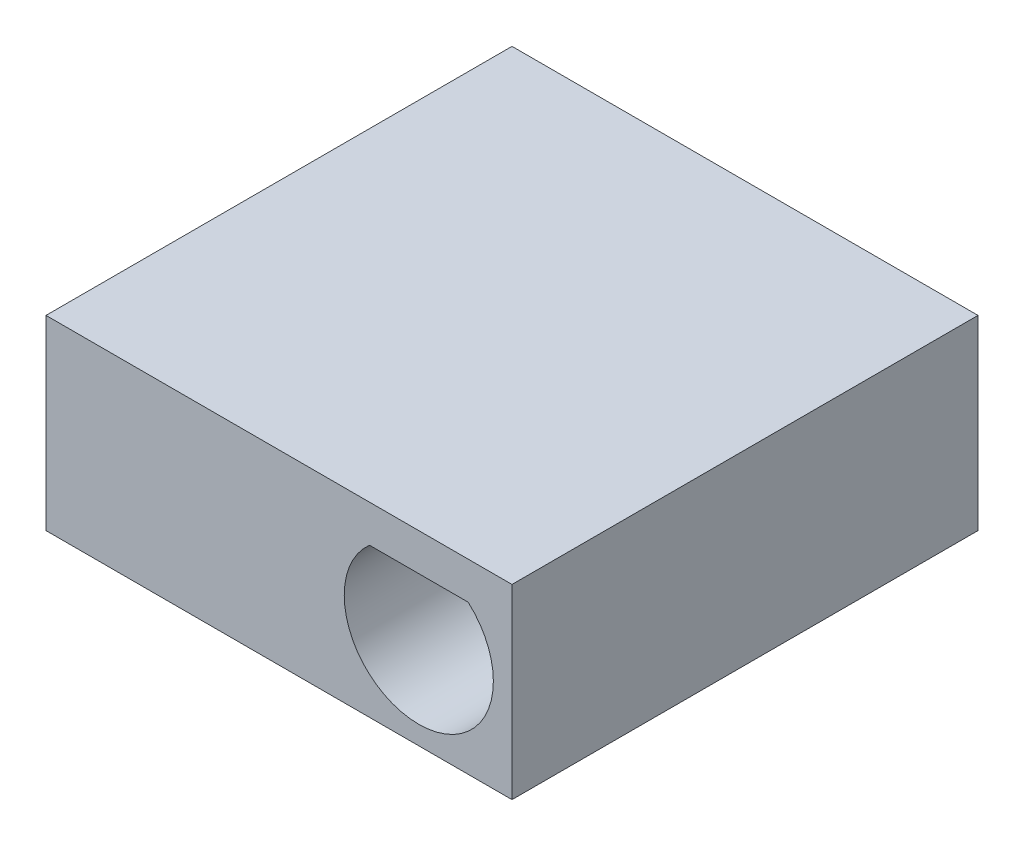
SolidWorks part; units mm, degrees
ref_plane "Front Plane" through (0, 0, 0) normal (0, 0, 1) x (1, 0, 0)
ref_plane "Top Plane" through (0, 0, 0) normal (0, 1, 0) x (1, 0, 0)
ref_plane "Right Plane" through (0, 0, 0) normal (1, 0, 0) x (0, 0, -1)
sketch "Sketch1" plane through (0, 0, 0) normal (0, 1, 0) x (1, 0, 0)
  line L1 (-12.5, -12.5) -> (12.5, -12.5)
  line L2 (-12.5, -12.5) -> (-12.5, 12.5)
  line L3 (-12.5, 12.5) -> (12.5, 12.5)
  line L4 (12.5, -12.5) -> (12.5, 12.5)
  line L5 (-12.5, -12.5) -> (12.5, 12.5) construction
  line L6 (-12.5, 12.5) -> (12.5, -12.5) construction
  point P0 (0, 0)
  dimension "D1" = 25
  dimension "D2" = 25
extrude "Boss-Extrude1" add sketch "Sketch1" along normal blind 10
sketch "Sketch2" plane through (0, 0, 12.5) normal (0, 0, 1) x (1, 0, 0)
  line L0 (12.5, 5) -> (7.5, 5) construction
  line L1 (12.5, 10) -> (12.5, 0) construction
  line L2 (7.5, 1) -> (7.5, 8) construction
  line L4 (4.8542, 8) -> (10.1458, 8)
  arc A1 (4.8542, 8) -> (10.1458, 8) centre (7.5, 5) ccw
  point P10 (7.5, 8)
  point P11 (7.5, 8)
  dimension "D2" = 8
  dimension "D1" = 5
  dimension "D3" = 7
  dimension "D4" = 5.2915
extrude "Cut-Extrude1" cut sketch "Sketch2" against normal blind 10
